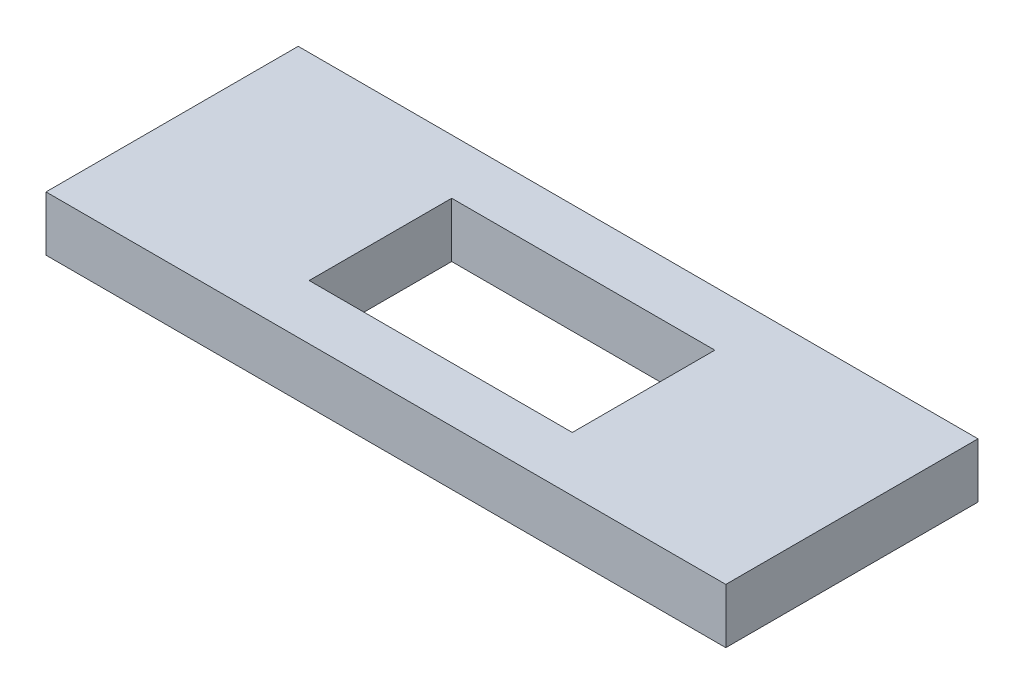
SolidWorks part; units mm, degrees
ref_plane "Front Plane" through (0, 0, 0) normal (0, 0, 1) x (1, 0, 0)
ref_plane "Top Plane" through (0, 0, 0) normal (0, 1, 0) x (1, 0, 0)
ref_plane "Right Plane" through (0, 0, 0) normal (1, 0, 0) x (0, 0, -1)
sketch "Sketch4" plane through (0, 0, 0) normal (0, 1, 0) x (1, 0, 0)
  line L1 (0, 0) -> (62, 0)
  line L2 (0, 0) -> (0, 23)
  line L3 (0, 23) -> (62, 23)
  line L4 (62, 0) -> (62, 23)
  line L5 (19, 18) -> (43, 18)
  line L6 (19, 18) -> (19, 5)
  line L7 (19, 5) -> (43, 5)
  line L8 (43, 18) -> (43, 5)
  line L9 (19, 18) -> (43, 5) construction
  line L10 (19, 5) -> (43, 18) construction
  point P5 (31, 11.5)
  point P10 (31, 0)
  point P11 (0, 11.5)
  dimension "D1" = 62
  dimension "D2" = 23
  dimension "D3" = 24
  dimension "D4" = 13
extrude "Boss-Extrude2" add sketch "Sketch4" along normal blind 5
sketch "Sketch5" plane through (0, 5, 0) normal (0, 1, 0) x (1, 0, 0)
  line L0 (0, 11.95) -> (62, 11.95) construction
  line L1 (0, -2.75) -> (0, 2.75) construction
  line L2 (62, 0) -> (62, 23) construction
  circle A0 centre (17.9, 11.95) radius 1.1
  circle A1 centre (45.6, 11.95) radius 1.1
  circle A2 centre (7, 11.95) radius 1.5
  circle A3 centre (55, 11.95) radius 1.5
  dimension "D1" = 3
  dimension "D3" = 3
  dimension "D2" = 7
  dimension "D4" = 7
extrude "Cut-Extrude1" cut sketch "Sketch5" against normal blind 10 rebuild error yes
ref_plane "Plane1" through (43, 5, -18) normal (-1, 0, 0) x (0, 0, 1)
